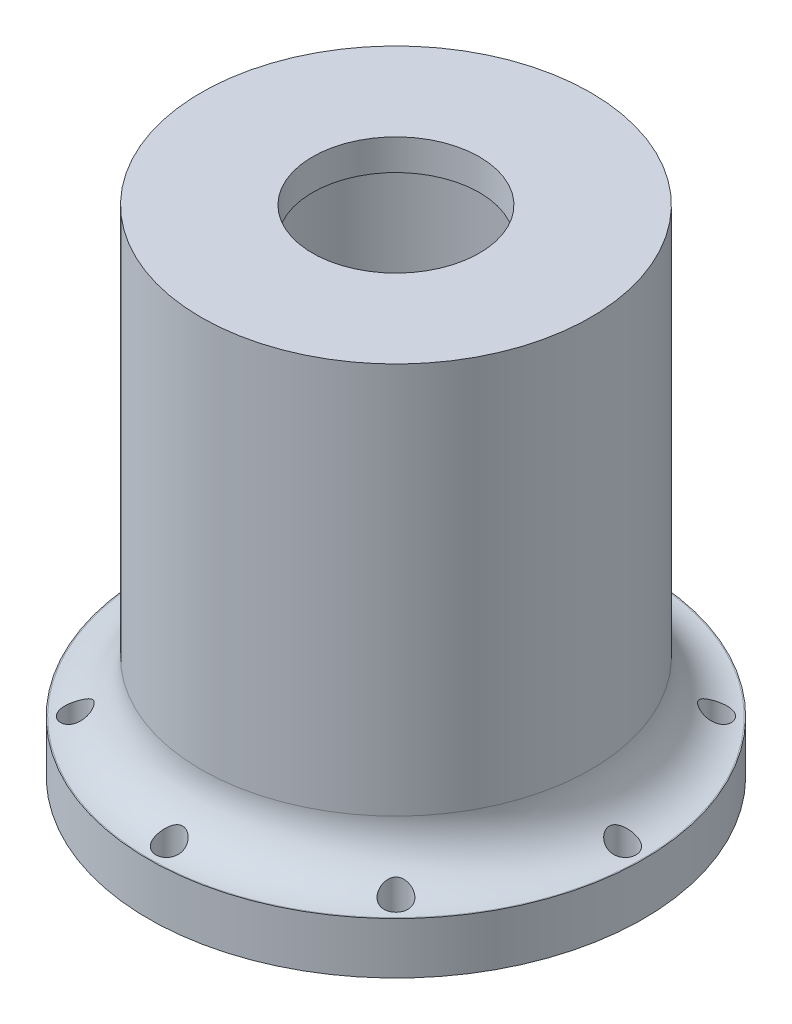
SolidWorks part; units mm, degrees
ref_plane "Front Plane" through (0, 0, 0) normal (0, 0, 1) x (1, 0, 0)
ref_plane "Top Plane" through (0, 0, 0) normal (0, 1, 0) x (1, 0, 0)
ref_plane "Right Plane" through (0, 0, 0) normal (1, 0, 0) x (0, 0, -1)
ref_axis "Axe1" through (0, -1.825, 0) along (0, 1, 0)
sketch "Esquisse1" plane through (0, 0, 0) normal (0, 0, 1) x (1, 0, 0)
  line L0 (13.9, 0) -> (13.9, 45)
  line L1 (13.9, 45) -> (8.1, 45)
  line L2 (8.1, 45) -> (8.1, 48)
  line L3 (8.1, 48) -> (18.9, 48)
  line L4 (18.9, 48) -> (18.9, 5)
  line L5 (18.9, 5) -> (24, 5)
  line L6 (24, 5) -> (24, 0)
  line L7 (24, 0) -> (13.9, 0)
  line L8 (0, -1.825) -> (0, 38.325) construction
  dimension "D1" = 13.9
  dimension "D2" = 8.1
  dimension "D3" = 3
  dimension "D4" = 5
  dimension "D5" = 24
  dimension "D6" = 5
  dimension "D7" = 45
revolve "Révolution1" add sketch "Esquisse1" angle 360 about axis through (0, -1.825, 0) along (0, 1, 0)
fillet "Congé3" radius 5 1 edges at (0, 5, -18.9)
sketch "Esquisse4" plane through (0, 0, 0) normal (0, -1, 0) x (-1, 0, 0)
  circle A0 centre (0, -22) radius 1.3
  dimension "D1" = 2.6
  dimension "D2" = 22
extrude "Enlèv. mat.-Extru.1" cut sketch "Esquisse4" against normal through all
pattern_circular "Répétition circulaire2" count 8 every 45 about axis through (0, -1.825, 0) along (0, 1, 0) of "Enlèv. mat.-Extru.1"
